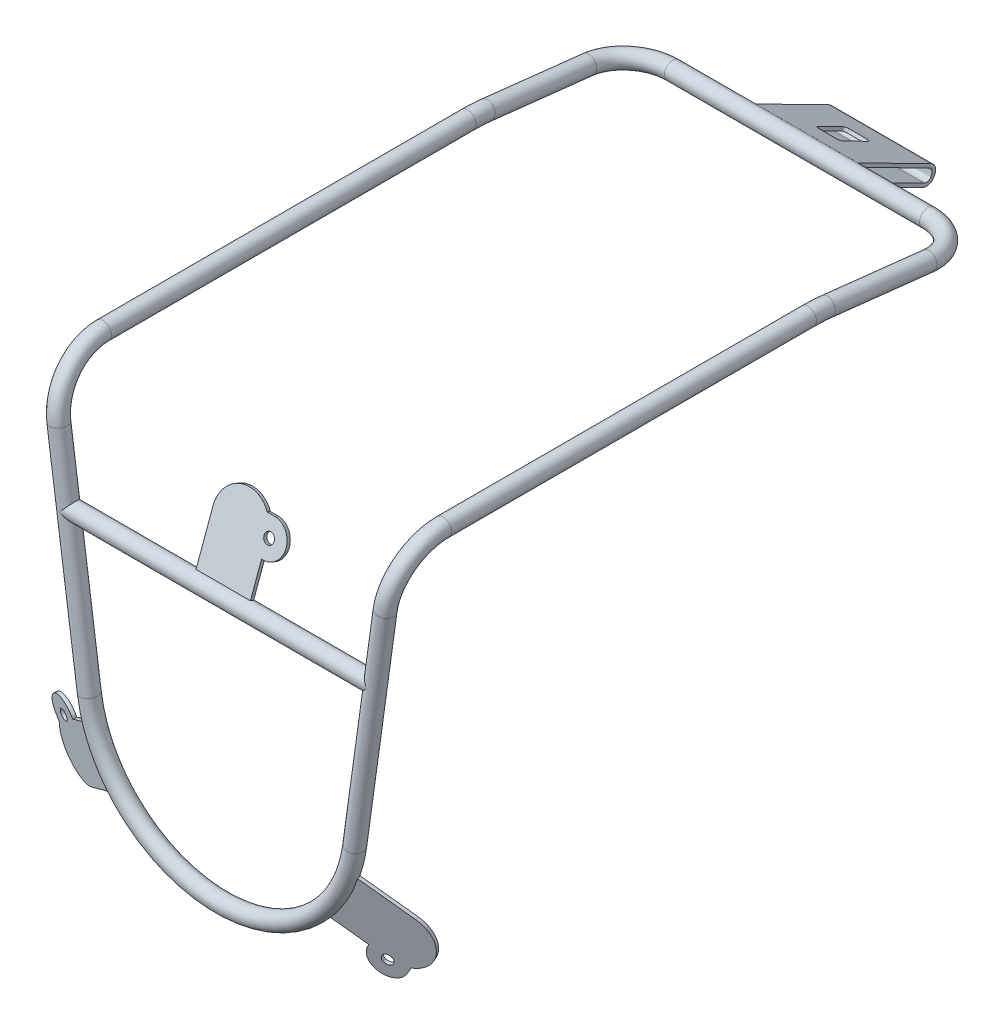
SolidWorks part; units mm, degrees
ref_plane "前视基准面" through (0, 0, 0) normal (0, 0, 1) x (1, 0, 0)
ref_plane "上视基准面" through (0, 0, 0) normal (0, 1, 0) x (1, 0, 0)
ref_plane "右视基准面" through (0, 0, 0) normal (1, 0, 0) x (0, 0, -1)
sketch3d "3D草图1"
  line L0 (100, 0, -30) -> (100, 0, -244.4615)
  line L1 (-100, 0, -30) -> (-100, 0, -244.4615)
  line L2 (75, -10, -340) -> (-75, -10, -340)
  line L5 (-95.8729, -29.7148, 0) -> (-77.9891, -158.4788, 0)
  line L6 (95.8729, -29.7148, 0) -> (77.9891, -158.4788, 0)
  line L7 (100, -0.6116, -255.5046) -> (100, -7.2392, -315.1529)
  line L9 (-100, -0.6116, -255.5046) -> (-100, -7.2392, -315.1529)
  arc A1 (-75, -10, -340) -> (-100, -7.2392, -315.1529) centre (-75, -7.2392, -315.1529) ccw
  arc A2 (75, -10, -340) -> (100, -7.2392, -315.1529) centre (75, -7.2392, -315.1529) ccw
  arc A3 (95.8729, -29.7148, 0) -> (100, 0, -30) centre (95.8729, -29.7148, -30) ccw
  arc A4 (-100, 0, -30) -> (-95.8729, -29.7148, 0) centre (-95.8729, -29.7148, -30) ccw
  arc A5 (100, -0.6116, -255.5046) -> (100, 0, -244.4615) centre (100, -100, -244.4615) ccw
  arc A6 (-100, 0, -244.4615) -> (-100, -0.6116, -255.5046) centre (-100, -100, -244.4615) ccw
  arc A7 (-77.9891, -158.4788, 0) -> (77.9891, -158.4788, 0) centre (0, -147.6469, 0) ccw
  point P12 (-100, -10, -340)
  point P13 (-75, 17.6079, -317.9137)
  point P16 (100, -10, -340)
  point P17 (75, -32.0863, -312.3921)
  point P20 (100, 0, 0)
  point P21 (66.1582, -25.5877, -30)
  point P24 (-100, 0, 0)
  point P25 (-66.1582, -25.5877, -30)
  point P28 (100, 0, -250)
  point P29 (200, -100, -244.4615)
  point P32 (-100, 0, -250)
  point P33 (-200, -100, -244.4615)
  point P39 (0, -147.6469, 78.7377)
  dimension "D2" = 25
  dimension "D4" = 30
  dimension "D5" = 100
  dimension "D1" = 250
  dimension "D3" = 250
  dimension "D6" = 130
ref_plane "基准面1" through (-100, 0, 0) normal (-1, 0, 0) x (0, 0, 1)
ref_plane "基准面2" through (0, 0, 0) normal (-1, 0, 0) x (0, 0, 1)
sketch "草图1" plane through (0, 0, 0) normal (-1, 0, 0) x (0, 0, 1)
  circle A0 centre (-340, -10) radius 5
sweep "扫描1" add profiles "草图1" path "3D草图1"
ref_plane "基准面3" through (0, -70, 0) normal (0, 1, 0) x (1, 0, 0)
sketch "草图2" plane through (0, -70, 0) normal (0, 1, 0) x (1, 0, 0)
  line L0 (-90.2605, 0) -> (90.2605, 0)
ref_plane "基准面6" through (90.2605, -70, 0) normal (1, 0, 0) x (0, 0, -1)
sketch "草图8" plane through (90.2605, -70, 0) normal (1, 0, 0) x (0, 0, -1)
  circle A0 centre (0, -0.0156) radius 5
sweep "扫描5" add profiles "草图8" path "草图2"
ref_plane "基准面7" through (0, -8.1884, -22.4976) normal (0, -0.342, -0.9397) x (1, 0, 0)
sketch "草图9" plane through (0, -8.1884, -22.4976) normal (0, -0.342, -0.9397) x (1, 0, 0)
  line L0 (0, 65.7785) -> (0, 41.6518) construction
  line L1 (-90.2605, 65.7785) -> (90.2605, 65.7785) construction
  line L2 (-16, 65.7785) -> (16, 65.7785)
  line L3 (16, 65.7785) -> (16, 41.7785)
  line L4 (-16, 65.7785) -> (-16, 31.7785)
  line L5 (0, 31.7785) -> (3, 31.7785) construction
  line L6 (12.49, 21.7785) -> (17, 21.7785)
  line L7 (16, 41.7785) -> (17, 41.7785)
  line L8 (0, 41.7785) -> (17, 41.7785) construction
  line L10 (0, 31.7785) -> (17, 31.7785) construction
  line L11 (0, 21.7785) -> (17, 21.7785) construction
  arc A0 (-16, 31.7785) -> (12.49, 21.7785) centre (0, 31.7785) ccw
  arc A2 (17, 41.7785) -> (17, 21.7785) centre (17, 31.7785) cw
  circle A3 centre (17, 31.7785) radius 3
  dimension "D1" = 10
  dimension "D2" = 10
extrude "凸台-拉伸1" add sketch "草图9" along normal mid plane 2
sketch "草图13" plane through (0, 0, 0) normal (0, 0, 1) x (1, 0, 0)
  line L0 (0, -38.3925) -> (0, -147.6469) construction
  line L1 (94.6172, -202.2742) -> (0, -147.6469) construction
  line L2 (-94.6172, -202.2742) -> (0, -147.6469) construction
  line L3 (-67.2442, -186.4704) -> (-41.6129, -230.8652) construction
  line L4 (67.2442, -186.4704) -> (58.1199, -202.2742) construction
  circle A0 centre (0, -147.6469) radius 77.6469
  circle A1 centre (0, -147.6469) radius 109.2545
  point P10 (0, -147.6469)
  dimension "D1" = 3
ref_axis "基准轴1" through (0, -147.6469, 0) along (0, 0, 1)
pattern_circular "阵列(圆周)2" count 3 every 120 about axis through (0, -147.6469, 0) along (0, 0, 1) of "凸台-拉伸1"
ref_axis "基准轴2" through (0, -40.1512, -17.4006) along (0, 0.342, 0.9397)
ref_axis "基准轴3" through (-94.1285, -201.9921, -14.1187) along (-0.2962, -0.171, 0.9397)
ref_axis "基准轴4" through (94.0633, -201.9544, -14.3255) along (0.2962, -0.171, 0.9397)
sketch "草图14" plane through (0, 0, 0) normal (1, 0, 0) x (0, 0, -1)
  line L0 (340.5522, -5.0306) -> (386.7783, -28.5633)
  line L1 (388.9658, -35.2875) -> (388.5844, -36.0368)
  line L2 (381.8602, -38.2243) -> (361.742, -27.9826)
  line L3 (339.6448, -6.8129) -> (385.871, -30.3456)
  line L4 (387.1835, -34.3801) -> (386.802, -35.1294)
  line L5 (382.7675, -36.4419) -> (362.6493, -26.2002)
  line L6 (340.5522, -5.0306) -> (339.6448, -6.8129)
  arc A0 (388.5844, -36.0368) -> (381.8602, -38.2243) centre (384.1285, -33.7684) cw
  arc A1 (386.7783, -28.5633) -> (388.9658, -35.2875) centre (384.51, -33.0191) cw
  arc A2 (385.871, -30.3456) -> (387.1835, -34.3801) centre (384.51, -33.0191) cw
  arc A3 (386.802, -35.1294) -> (382.7675, -36.4419) centre (384.1285, -33.7684) cw
  spline S0 degree 1 poles (362.6493, -26.2002) (361.742, -27.9826) knots 0 0 1 1
  point P17 (0, 0)
  dimension "D1" = 5
  dimension "D2" = 2
extrude "凸台-拉伸2" add sketch "草图14" along normal blind 30 and the other way blind 30
sketch "草图15" plane through (0, 133.6897, -68.0583) normal (0, 0.8912, -0.4537) x (1, 0, 0)
  line L1 (5.5, 323.1804) -> (-5.5, 323.1804)
  line L2 (7.5, 325.1804) -> (7.5, 341.1804)
  line L3 (5.5, 343.1804) -> (-5.5, 343.1804)
  line L4 (-7.5, 325.1804) -> (-7.5, 341.1804)
  line L5 (7.5, 323.1804) -> (-7.5, 343.1804) construction
  line L6 (7.5, 343.1804) -> (-7.5, 323.1804) construction
  arc A0 (-5.5, 323.1804) -> (-7.5, 325.1804) centre (-5.5, 325.1804) cw
  arc A1 (5.5, 323.1804) -> (7.5, 325.1804) centre (5.5, 325.1804) ccw
  arc A2 (7.5, 341.1804) -> (5.5, 343.1804) centre (5.5, 341.1804) ccw
  arc A3 (-5.5, 343.1804) -> (-7.5, 341.1804) centre (-5.5, 341.1804) ccw
  point P0 (0, 333.1804)
  dimension "D1" = 2
extrude "切除-拉伸1" cut sketch "草图15" against normal blind 5
sketch "草图16" plane through (0, 0, 0) normal (1, 0, 0) x (0, 0, -1)
  circle A0 centre (347.7974, -13.5117) radius 2.7782
